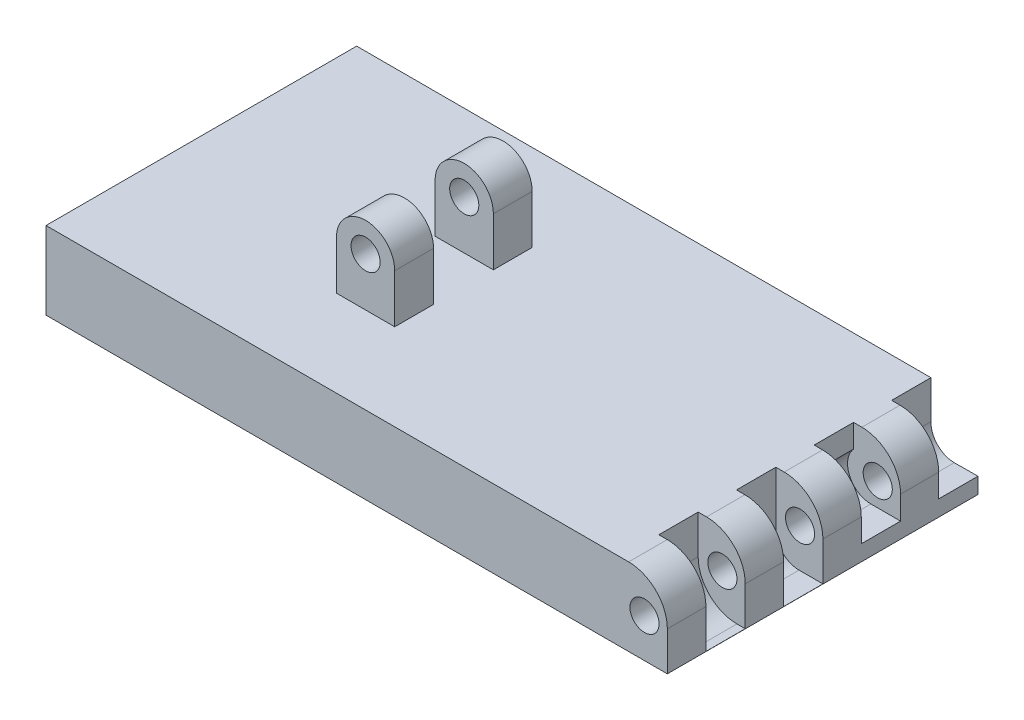
SolidWorks part; units mm, degrees
material "6061-T6 (SS)"
ref_plane "Front Plane" through (0, 0, 0) normal (0, 0, 1) x (1, 0, 0)
ref_plane "Top Plane" through (0, 0, 0) normal (0, 1, 0) x (1, 0, 0)
ref_plane "Right Plane" through (0, 0, 0) normal (1, 0, 0) x (0, 0, -1)
sketch "Sketch1" plane through (0, 0, 0) normal (0, 0, 1) x (1, 0, 0)
  line L1 (0, 0) -> (95.2754, 0)
  line L2 (0, 0) -> (0, -12.7)
  line L3 (0, -12.7) -> (101.6, -12.7)
  line L4 (101.6, -6.3246) -> (101.6, -12.7)
  arc A1 (101.6, -6.3246) -> (95.2754, 0) centre (95.2754, -6.3246) ccw
  point P7 (0, 0)
  point P10 (101.6, 0)
  dimension "D4" = 6.3754
  dimension "D1" = 12.7
  dimension "D2" = 101.6
extrude "Boss-Extrude1" add sketch "Sketch1" along normal blind 50.8
ref_plane "Plane1" through (0, 0, 41.275) normal (0, 0, 1) x (1, 0, 0)
sketch "Sketch2" plane through (0, 0, 50.8) normal (0, 0, 1) x (1, 0, 0)
  line L0 (0, -12.7) -> (101.6, -12.7) construction
  line L1 (101.6, -12.7) -> (101.6, -6.3246) construction
  circle A0 centre (97.8662, -6.3246) radius 2.3813
  dimension "D1" = 4.7625
  dimension "D2" = 6.3754
  dimension "D3" = 3.7338
extrude "Cut-Extrude1" cut sketch "Sketch2" against normal blind 50.8
sketch "Sketch3" plane through (0, 0, 41.275) normal (0, 0, 1) x (1, 0, 0)
  line L0 (101.6, -12.6746) -> (100.2411, -12.6746)
  line L1 (101.6, -12.7) -> (101.6, -6.3246) construction
  line L2 (101.6, -12.6746) -> (101.6, 0)
  line L3 (101.6, 0) -> (95.2754, 0)
  line L5 (93.9038, -6.3373) -> (93.9038, 0)
  line L6 (95.2754, 0) -> (0, 0) construction
  line L7 (93.9038, 0) -> (95.2754, 0)
  line L8 (0, -12.7) -> (101.6, -12.7) construction
  arc A0 (100.2411, -12.6746) -> (93.9038, -6.3373) centre (100.2411, -6.3373) cw
  dimension "D2" = 6.3627
  dimension "D1" = 7.6962
extrude "Cut-Extrude2" cut sketch "Sketch3" along normal mid plane 6.4262
ref_plane "Plane2" through (0, 0, 28.575) normal (0, 0, 1) x (1, 0, 0)
sketch "Sketch4" plane through (0, 0, 28.575) normal (0, 0, 1) x (1, 0, 0)
  line L0 (101.6, -12.6746) -> (97.7015, -12.6746)
  line L1 (101.6, -12.6746) -> (101.6, 0)
  line L3 (93.9038, -8.8663) -> (93.9038, 0)
  line L4 (95.2754, 0) -> (0, 0) construction
  line L5 (93.9038, 0) -> (101.6, 0)
  arc A0 (97.7015, -12.6746) -> (93.9038, -8.8663) centre (97.7015, -8.8769) cw
  point P3 (101.6, -6.3373)
  dimension "D4" = 3.7977
  dimension "D2" = 7.6962
extrude "Cut-Extrude3" cut sketch "Sketch4" against normal mid plane 6.4262
ref_plane "Plane3" through (0, 0, 15.875) normal (0, 0, 1) x (1, 0, 0)
sketch "Sketch5" plane through (0, 0, 15.875) normal (0, 0, 1) x (1, 0, 0)
  line L4 (101.6, -10.1346) -> (101.6, 0)
  line L5 (101.6, 0) -> (93.9038, 0)
  line L6 (95.2754, 0) -> (0, 0) construction
  line L8 (93.9038, 0) -> (93.9038, -3.7846)
  line L12 (101.6, -12.7) -> (101.6, -6.3246) construction
  line L13 (96.7436, -10.1346) -> (101.6, -10.1346)
  line L14 (0, -12.7) -> (101.6, -12.7) construction
  arc A1 (96.7436, -10.1346) -> (93.9038, -3.7846) centre (96.7436, -6.3246) cw
  dimension "D2" = 3.81
  dimension "D1" = 7.6962
  dimension "D3" = 6.3754
extrude "Cut-Extrude4" cut sketch "Sketch5" against normal mid plane 6.4262
ref_plane "Plane4" through (0, 0, 0) normal (0, 0, 1) x (1, 0, 0)
sketch "Sketch6" plane through (0, 0, 0) normal (0, 0, 1) x (1, 0, 0)
  line L1 (97.7128, -10.1346) -> (101.6, -10.1032)
  line L2 (101.6, -10.1032) -> (101.6, 0)
  line L3 (101.6, 0) -> (93.9038, 0)
  line L4 (95.2754, 0) -> (0, 0) construction
  line L5 (93.9038, 0) -> (93.9038, -6.2352)
  line L6 (101.6, -12.7) -> (101.6, -6.3246) construction
  line L7 (0, -12.7) -> (101.6, -12.7) construction
  arc A0 (93.9038, -6.2352) -> (97.7128, -10.1346) centre (97.7128, -6.3246) ccw
  dimension "D1" = 3.81
  dimension "D2" = 6.3754
  dimension "D3" = 7.6962
  dimension "D4" = 3.8874
extrude "Cut-Extrude5" cut sketch "Sketch6" along normal blind 6.4262
ref_plane "Plane5" through (0, 0, 25.4) normal (0, 0, -1) x (-1, 0, 0)
sketch "Sketch7" plane through (0, 0, 25.4) normal (0, 0, -1) x (-1, 0, 0)
  line L0 (-38.1, 16.4881) -> (-38.1, -23.6149) construction
  line L1 (-101.6, -12.7) -> (-101.6, -10.1032) construction
  line L2 (-42.8625, 0) -> (-42.8625, 7.9375)
  line L3 (-93.9038, 0) -> (0, 0) construction
  line L4 (-33.3375, 0) -> (-33.3375, 7.9375)
  line L5 (-42.8625, 0) -> (-33.3375, 0)
  circle A0 centre (-38.1, 7.9375) radius 2.3812
  arc A1 (-42.8625, 7.9375) -> (-33.3375, 7.9375) centre (-38.1, 7.9375) cw
  dimension "D2" = 4.7625
  dimension "D1" = 63.5
  dimension "D3" = 4.7625
  dimension "D4" = 4.7625
  dimension "D5" = 7.9375
extrude "Boss-Extrude2" add sketch "Sketch7" along normal mid plane 22.479
sketch "Sketch8" plane through (0, 0, 28.575) normal (0, 0, 1) x (1, 0, 0)
ref_plane "Plane6" through (0, 0, 25.4) normal (0, 0, -1) x (-1, 0, 0)
sketch "Sketch10" plane through (0, 0, 25.4) normal (0, 0, -1) x (-1, 0, 0)
  line L0 (-42.8625, 7.9375) -> (-42.8625, 0)
  line L1 (-42.8625, 0) -> (-33.3375, 0)
  line L2 (-33.3375, 0) -> (-33.3375, 7.9375)
  arc A0 (-42.8625, 7.9375) -> (-33.3375, 7.9375) centre (-38.1, 7.9375) cw
  circle A1 centre (-38.1, 7.9375) radius 2.3812
extrude "Cut-Extrude6" cut sketch "Sketch10" against normal mid plane 9.779
sketch "Sketch11" plane through (0, -12.7, 0) normal (0, -1, 0) x (1, 0, 0)
  line L0 (88.9, -6.7419) -> (88.9, 64.1901) construction
  line L1 (12.7, -8.26) -> (12.7, 63.0908) construction
  line L2 (101.6, 25.3619) -> (0, 25.4) construction
  line L3 (0, 50.8) -> (0, 0) construction
  line L4 (101.6, 50.8) -> (101.6, 0) construction
  dimension "D1" = 12.7
  dimension "D2" = 12.7
hole_wizard "1/4 (0.25) Diameter Hole1" positions "Sketch12" profile "Sketch13" hole size "1/4" standard "ANSI Inch"
sketch "Sketch12" plane through (0, -12.7, 0) normal (0, -1, 0) x (-1, 0, 0)
  line L0 (-88.9, 6.7419) -> (-88.9, -64.1901) construction
  line L1 (-12.7, 8.26) -> (-12.7, -63.0908) construction
  line L2 (-101.6, -25.3619) -> (0, -25.4) construction
  point P0 (-88.9, -12.6667)
  point P4 (-88.9, -38.0667)
  point P6 (-12.7, -38.0952)
  point P10 (-12.7, -12.6952)
  dimension "D1" = 12.7
  dimension "D2" = 12.7
  dimension "D3" = 12.7
  dimension "D4" = 12.7
sketch "Sketch13" plane through (88.9, -12.7, 12.6667) normal (1, 0, 0) x (0, 0, -1)
  line L0 (0, 0) -> (0, 11.4327)
  line L1 (0, 11.4327) -> (3.175, 9.525)
  line L2 (3.175, 9.525) -> (3.175, 0)
  line L5 (3.175, 0) -> (0, 0)
  line L10 (0, 11.4327) -> (-3.175, 9.525) construction
  line L11 (0, -6.35) -> (0, 107.95) construction
  dimension "Hole Dia." = 6.35
  dimension "Hole Depth" = 9.525
  dimension "Drill Angle" = 118
thread "Thread1" pitch 0.9071 method extrude profile "Thread Profile1" start angle 0, offset 0, length 0, pitch 0.9071, diameter 6.35
ref_plane "Plane7" through (92.075, -12.7, 12.6667) normal (0, 0, 1) x (1, 0, 0)
sketch "Thread Profile1" plane through (92.075, -12.7, 12.6667) normal (0, 0, 1) x (1, 0, 0)
  line L0 (0, 0) -> (0, 0.9071) construction
  line L11 (0, 0) -> (0, 0.7937)
  line L12 (0, 0.7937) -> (-0.491, 0.5103)
  line L13 (-0.491, 0.5103) -> (-0.491, 0.2835)
  line L15 (-0.491, 0.2835) -> (0, 0)
  line L17 (-0.491, 0.3969) -> (0, 0.3969) construction
  point P2 (0, 0)
  dimension "Pitch" = 0.9071
  dimension "Profile_Angle" = 60
  dimension "Profile_Land" = 0.2268
  dimension "Profile_Height" = 0.491
thread "Thread2" pitch 0.9071 method extrude profile "Thread Profile2" start angle 0, offset 0, length 0, pitch 0.9071, diameter 6.35
ref_plane "Plane8" through (92.075, -12.7, 38.0667) normal (0, 0, 1) x (1, 0, 0)
sketch "Thread Profile2" plane through (92.075, -12.7, 38.0667) normal (0, 0, 1) x (1, 0, 0)
  line L0 (0, 0) -> (0, 0.9071) construction
  line L11 (0, 0) -> (0, 0.7937)
  line L12 (0, 0.7937) -> (-0.491, 0.5103)
  line L13 (-0.491, 0.5103) -> (-0.491, 0.2835)
  line L15 (-0.491, 0.2835) -> (0, 0)
  line L17 (-0.491, 0.3969) -> (0, 0.3969) construction
  point P2 (0, 0)
  dimension "Pitch" = 0.9071
  dimension "Profile_Angle" = 60
  dimension "Profile_Land" = 0.2268
  dimension "Profile_Height" = 0.491
thread "Thread3" pitch 0.9071 method extrude profile "Thread Profile3" start angle 0, offset 0, length 0, pitch 0.9071, diameter 6.35
ref_plane "Plane9" through (15.875, -12.7, 12.6952) normal (0, 0, 1) x (1, 0, 0)
sketch "Thread Profile3" plane through (15.875, -12.7, 12.6952) normal (0, 0, 1) x (1, 0, 0)
  line L0 (0, 0) -> (0, 0.9071) construction
  line L11 (0, 0) -> (0, 0.7937)
  line L12 (0, 0.7937) -> (-0.491, 0.5103)
  line L13 (-0.491, 0.5103) -> (-0.491, 0.2835)
  line L15 (-0.491, 0.2835) -> (0, 0)
  line L17 (-0.491, 0.3969) -> (0, 0.3969) construction
  point P2 (0, 0)
  dimension "Pitch" = 0.9071
  dimension "Profile_Angle" = 60
  dimension "Profile_Land" = 0.2268
  dimension "Profile_Height" = 0.491
thread "Thread4" pitch 0.9071 method extrude profile "Thread Profile4" start angle 0, offset 0, length 0, pitch 0.9071, diameter 6.35
ref_plane "Plane10" through (15.875, -12.7, 38.0952) normal (0, 0, 1) x (1, 0, 0)
sketch "Thread Profile4" plane through (15.875, -12.7, 38.0952) normal (0, 0, 1) x (1, 0, 0)
  line L0 (0, 0) -> (0, 0.9071) construction
  line L11 (0, 0) -> (0, 0.7937)
  line L12 (0, 0.7937) -> (-0.491, 0.5103)
  line L13 (-0.491, 0.5103) -> (-0.491, 0.2835)
  line L15 (-0.491, 0.2835) -> (0, 0)
  line L17 (-0.491, 0.3969) -> (0, 0.3969) construction
  point P2 (0, 0)
  dimension "Pitch" = 0.9071
  dimension "Profile_Angle" = 60
  dimension "Profile_Land" = 0.2268
  dimension "Profile_Height" = 0.491
